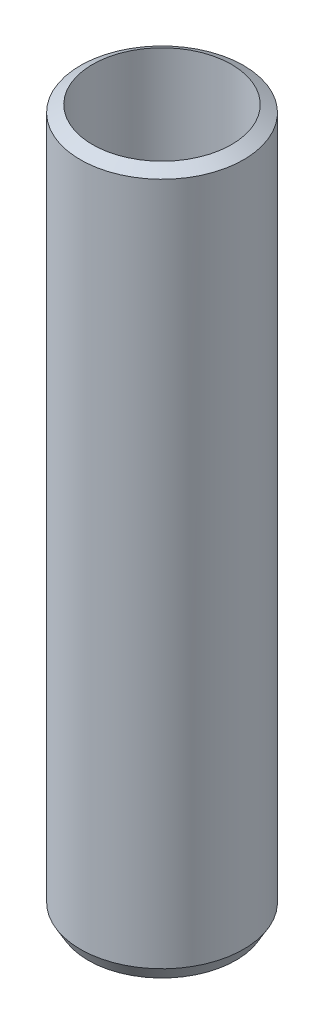
SolidWorks part; units mm, degrees
ref_plane "Front Plane" through (0, 0, 0) normal (0, 0, 1) x (1, 0, 0)
ref_plane "Top Plane" through (0, 0, 0) normal (0, 1, 0) x (1, 0, 0)
ref_plane "Right Plane" through (0, 0, 0) normal (1, 0, 0) x (0, 0, -1)
sketch "Sketch1" plane through (0, 0, 0) normal (0, 1, 0) x (1, 0, 0)
  circle A0 centre (0, 0) radius 60
  dimension "SHAFT_OD" = 120
extrude "Boss-Extrude1" add sketch "Sketch1" along normal blind 518.0701
sketch "Sketch2" plane through (0, 0, 0) normal (0, 1, 0) x (1, 0, 0)
  circle A0 centre (0, 0) radius 51.0685
  dimension "BORE_D" = 102.1371
extrude "Cut-Extrude1" cut sketch "Sketch2" along normal through all
chamfer "Chamfer1" distance 5.7437 angle 60 2 edges at (0, 518.0701, 60) (0, 0, 60) first distance on face at (0, 518.0701, 60) first distance on face at (0, 0, 51.0685)
